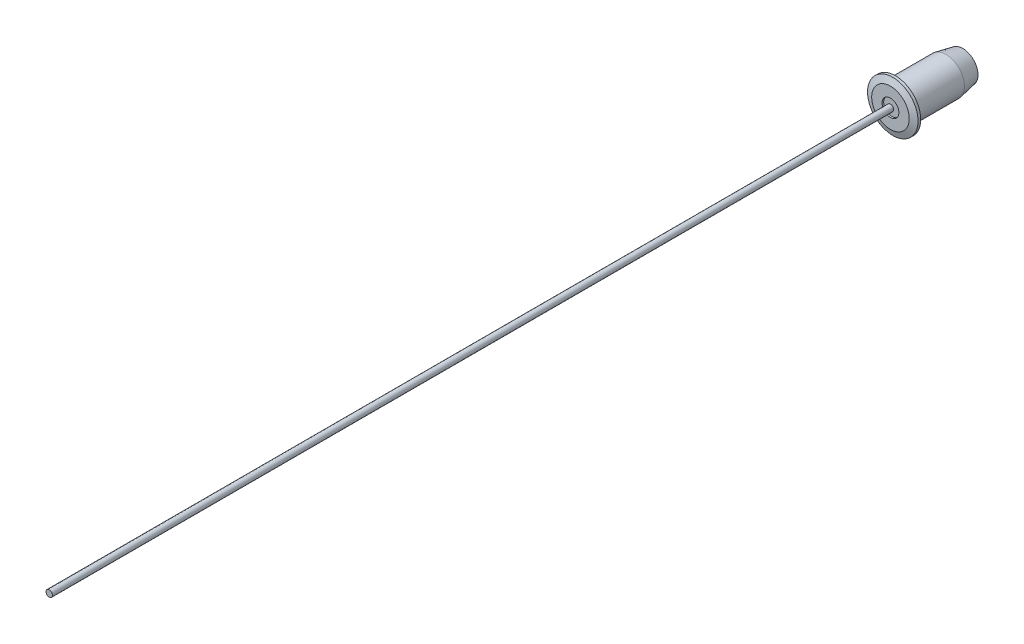
SolidWorks part; units mm, degrees
ref_plane "Front Plane" through (0, 0, 0) normal (0, 0, 1) x (1, 0, 0)
ref_plane "Top Plane" through (0, 0, 0) normal (0, 1, 0) x (1, 0, 0)
ref_plane "Right Plane" through (0, 0, 0) normal (1, 0, 0) x (0, 0, -1)
sketch "Sketch1" plane through (0, 0, 0) normal (0, 0, 1) x (1, 0, 0)
  circle A0 centre (0, 0) radius 7.5
  dimension "D1" = 15
extrude "Boss-Extrude1" add sketch "Sketch1" along normal blind 1.5
chamfer "Chamfer2" distance 0.7 angle 70 1 edges at (7.5, 0, 1.5) first distance on face at (7.5, 0, 1.5)
sketch "Sketch2" plane through (0, 0, 0) normal (0, 0, -1) x (-1, 0, 0)
  circle A0 centre (0, 0) radius 5.5
  dimension "D1" = 11
extrude "Boss-Extrude2" add sketch "Sketch2" along normal blind 20
chamfer "Chamfer3" distance 5 angle 11 1 edges at (-5.5, 0, -20) first distance on face at (-5.5, 0, -20)
sketch "Sketch3" plane through (0, 0, 1.5) normal (0, 0, 1) x (1, 0, 0)
  circle A0 centre (0, 0) radius 2.5
  dimension "D1" = 5
extrude "Cut-Extrude1" cut sketch "Sketch3" against normal blind 0.5
sketch "Sketch4" plane through (0, 0, 1.5) normal (0, 0, 1) x (1, 0, 0)
  circle A0 centre (0, 0) radius 0.25
  dimension "D1" = 0.5
extrude "Boss-Extrude3" [suppressed] add sketch "Sketch4" along normal blind 500 separate body
sketch "Sketch5" plane through (0, 0, 1.5) normal (0, 0, 1) x (1, 0, 0)
  circle A0 centre (0, 0) radius 0.9547
extrude "Boss-Extrude4" add sketch "Sketch5" along normal blind 250 separate body
